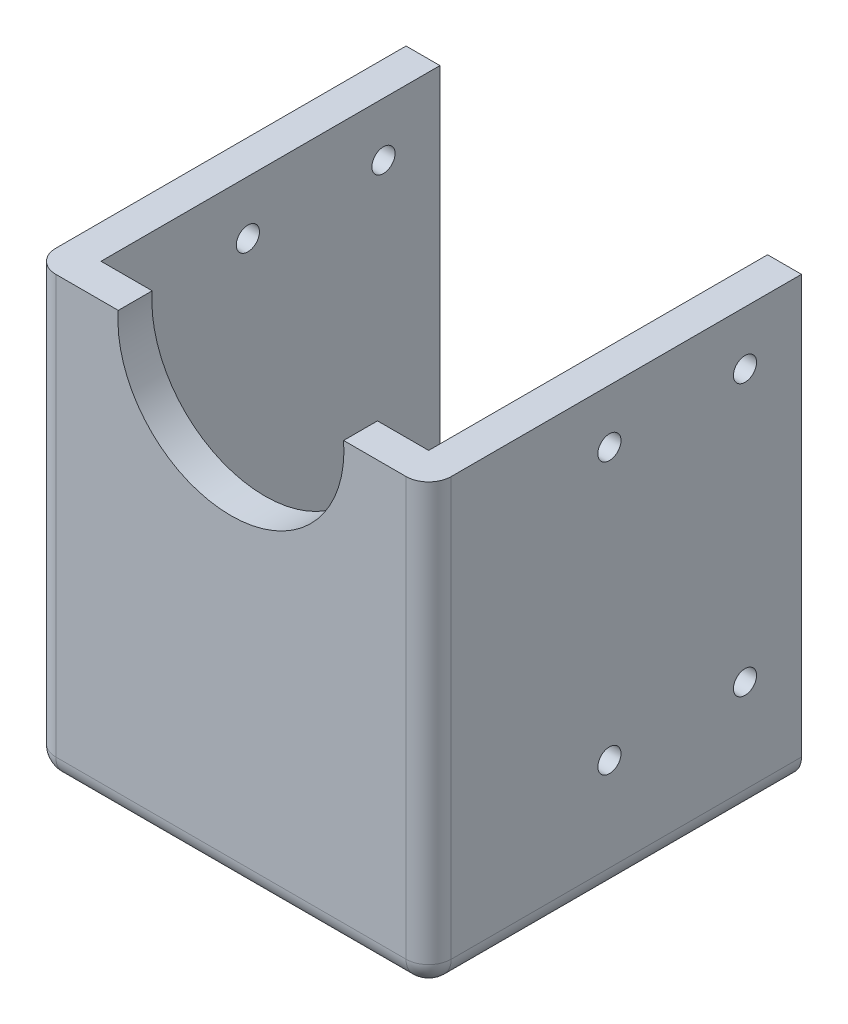
SolidWorks part; units mm, degrees
ref_plane "정면" through (0, 0, 0) normal (0, 0, 1) x (1, 0, 0)
ref_plane "윗면" through (0, 0, 0) normal (0, 1, 0) x (1, 0, 0)
ref_plane "우측면" through (0, 0, 0) normal (1, 0, 0) x (0, 0, -1)
sketch "스케치2" plane through (0, 0, 0) normal (0, 0, 1) x (1, 0, 0)
  line L0 (12.25, -35.25) -> (-12.25, -35.25) construction
  line L1 (14.75, -35.25) -> (-14.25, -35.25)
  line L2 (14.75, -35.25) -> (14.75, 0.75)
  line L3 (14.75, 0.75) -> (10.2218, 0.75)
  line L4 (-14.25, -35.25) -> (-14.25, 0.75)
  line L5 (14.75, -35.25) -> (-14.25, 0.75) construction
  line L6 (14.75, 0.75) -> (-14.25, -35.25) construction
  line L7 (-14.25, -33.25) -> (-14.25, -21) construction
  line L8 (-17.25, -38.25) -> (-17.25, 0.75)
  line L9 (-17.25, -38.25) -> (-17.25, 3.75) construction
  line L10 (17.75, -38.25) -> (17.75, 0.75)
  line L11 (17.75, -38.25) -> (-17.25, -38.25)
  line L12 (14.75, 0.75) -> (17.75, 0.75)
  line L13 (-14.25, 0.75) -> (-17.25, 0.75)
  line L14 (17.75, -38.25) -> (17.75, 3.75) construction
  line L15 (17.75, 3.75) -> (-17.25, 3.75) construction
  line L23 (-9.7218, 0.75) -> (-14.25, 0.75)
  line L24 (14.75, 0.75) -> (-14.25, 0.75) construction
  arc A0 (-9.7218, 0.75) -> (10.2218, 0.75) centre (0.25, 0) ccw
  point P0 (0.25, -17.25)
  dimension "D4" = 20
  dimension "D1" = 29
  dimension "D2" = 36
  dimension "D5" = 14.5
  dimension "D3" = 3
extrude "보스-돌출1" add sketch "스케치2" along normal blind 3 contours A0 L23 L4 L1 L2 L3 | L4 L13 L8 L11 L10 L12 L2 L1 region at (15.274, -17.25, 0) region at (0.25, -19.8959, 0)
extrude "보스-돌출2" add sketch "스케치2<6>" against normal blind 30 contours L4 L13 L8 L11 L10 L12 L2 L1 region at (15.274, -17.25, 0)
sketch "스케치2<6>" plane through (0, 0, 0) normal (0, 0, 1) x (1, 0, 0) same geometry as "스케치2"
sketch "스케치3" plane through (17.75, 0, 0) normal (1, 0, 0) x (0, 0, -1)
  line L0 (-3, 0.75) -> (30, 0.75) construction
  line L1 (30, -38.25) -> (30, 0.75) construction
  circle A0 centre (25, -4) radius 1.025
  circle A1 centre (13, -4) radius 1.025
  circle A2 centre (25, -28) radius 1.025
  circle A3 centre (13, -28) radius 1.025
  dimension "D1" = 2.05
  dimension "D2" = 4.75
  dimension "D3" = 5
  dimension "D4" = 12
  dimension "D5" = 24
extrude "컷-돌출1" cut sketch "스케치3" against normal blind 43
sketch "스케치4" plane through (0, -38.25, 0) normal (0, -1, 0) x (1, 0, 0)
  circle A0 centre (8.25, -25) radius 1.025
  circle A1 centre (-7.75, -25) radius 1.025
  circle A2 centre (-7.75, -13) radius 1.025
  circle A3 centre (8.25, -13) radius 1.025
  dimension "D1" = 2.05
extrude "컷-돌출2" cut sketch "스케치4" against normal blind 3
fillet "필렛1" radius 2 5 edges at (-17.25, -18.75, 3) (-17.25, -38.25, -13.5) (17.75, -38.25, -13.5) (0.25, -38.25, 3) (17.75, -18.75, 3)
